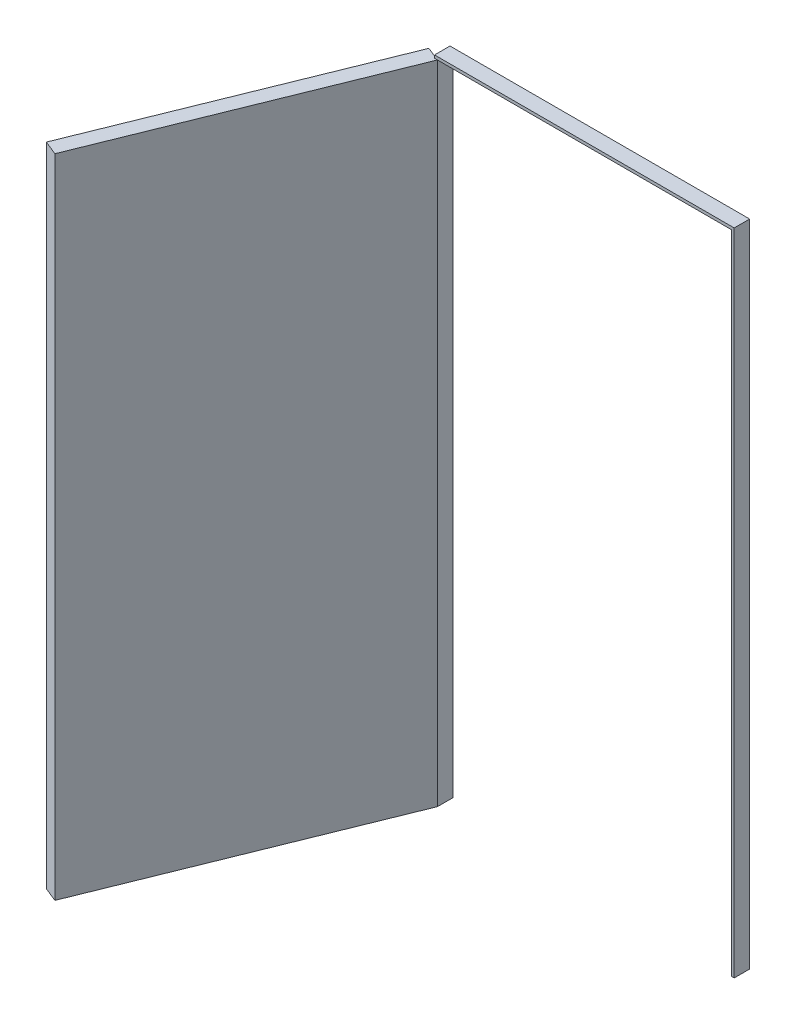
SolidWorks part; units mm, degrees
ref_plane "Front" through (0, 0, 0) normal (0, 0, 1) x (1, 0, 0)
ref_plane "Top" through (0, 0, 0) normal (0, 1, 0) x (1, 0, 0)
ref_plane "Right" through (0, 0, 0) normal (1, 0, 0) x (0, 0, -1)
sketch "Sketch1" plane through (0, 0, 0) normal (0, 0, 1) x (1, 0, 0)
  line L0 (965.2, 2114.55) -> (965.2, -2133.6)
  line L1 (-984.25, 2133.6) -> (984.25, 2133.6)
  line L2 (-984.25, 2133.6) -> (-984.25, -2133.6)
  line L3 (-984.25, -2133.6) -> (984.25, -2133.6) construction
  line L4 (984.25, 2133.6) -> (984.25, -2133.6)
  line L5 (-984.25, 2133.6) -> (984.25, -2133.6) construction
  line L6 (-984.25, -2133.6) -> (984.25, 2133.6) construction
  line L7 (-965.2, 2114.55) -> (965.2, 2114.55)
  line L8 (-965.2, 2114.55) -> (-965.2, -2133.6)
  line L9 (-984.25, -2133.6) -> (-965.2, -2133.6)
  line L10 (965.2, -2133.6) -> (984.25, -2133.6)
  point P0 (0, 0)
  dimension "D1" = 4267.2
  dimension "D3" = 1930.4
  dimension "D2" = 19.05
extrude "Boss-Extrude1" add sketch "Sketch1" along normal blind 101.6
sketch "Sketch2" plane through (0, -2133.6, 0) normal (0, -1, 0) x (1, 0, 0)
  line L0 (-965.2, 101.6) -> (-1688.3406, 1891.4357)
  line L1 (-1688.3406, 1891.4357) -> (-1782.5424, 1853.3757)
  line L2 (-1782.5424, 1853.3757) -> (-1059.4019, 63.54)
  line L3 (-1059.4019, 63.54) -> (-965.2, 101.6)
  line L4 (-965.2, 0) -> (965.2, 0) construction
  dimension "D1" = 101.6
  dimension "D2" = 112
extrude "Boss-Extrude2" add sketch "Sketch2" against normal up to surface (4248.15 mm away) separate body up to face at (0, 2114.55, 50.8)
sketch "Sketch3" plane through (-893.8758, 0, 2212.4203) normal (-0.3746, 0, 0.9272) x (0.9272, 0, 0.3746)
  line L0 (-958.4578, 2114.55) -> (-958.4578, -2133.6) construction
  line L1 (-958.4578, -787.4) -> (-1085.4578, -787.4)
  line L2 (-958.4578, -787.4) -> (-958.4578, -838.2)
  line L3 (-958.4578, -1117.6) -> (-1085.4578, -1117.6)
  line L4 (-1085.4578, -787.4) -> (-1085.4578, -1117.6)
  line L5 (-958.4578, -1066.8) -> (-958.4578, -1117.6)
  line L6 (-958.4578, -838.2) -> (-1034.6578, -838.2)
  line L8 (-958.4578, -1066.8) -> (-1034.6578, -1066.8)
  line L9 (-1034.6578, -838.2) -> (-1034.6578, -1066.8)
  line L10 (-1034.6578, -838.2) -> (-1085.4578, -838.2) construction
  line L11 (-1034.6578, -838.2) -> (-1034.6578, -787.4) construction
  line L12 (-1034.6578, -1066.8) -> (-1034.6578, -1117.6) construction
  line L13 (-856.8578, -2133.6) -> (-958.4578, -2133.6) construction
  dimension "D1" = 50.8
  dimension "D2" = 1016
  dimension "D3" = 76.2
  dimension "D4" = 330.2
extrude "Boss-Extrude3" add sketch "Sketch3" along normal blind 38.1 from offset 228.6 offset against normal yes
fillet "Fillet1" radius 38.1 2 edges at (-1821.796, -1117.6, 1611.5093) (-1821.796, -787.4, 1611.5093)
fillet "Fillet2" radius 12.7 2 edges at (-1774.695, -1066.8, 1630.5393) (-1774.695, -838.2, 1630.5393)
fillet "Fillet3" radius 12.7 20 edges at (-1726.3455, -1066.8, 1629.5277) (-1764.1099, -1063.0803, 1614.2699) (-1767.5588, -952.5, 1612.8764) (-1764.1099, -841.9197, 1614.2699) (-1726.3455, -838.2, 1629.5277) (-1738.1207, -787.4, 1624.7702) (-1804.3131, -798.5592, 1598.0267) (-1814.6597, -952.5, 1593.8464) (-1804.3131, -1106.4408, 1598.0267) (-1738.1207, -1117.6, 1624.7702) (-1818.5856, -798.5592, 1633.3524) (-1752.3932, -787.4, 1660.0959) (-1740.618, -838.2, 1664.8534) (-1778.3824, -841.9197, 1649.5956) (-1781.8313, -952.5, 1648.2021) (-1778.3824, -1063.0803, 1649.5956) (-1740.618, -1066.8, 1664.8534) (-1752.3932, -1117.6, 1660.0959) (-1818.5856, -1106.4408, 1633.3524) (-1828.9322, -952.5, 1629.1721)
